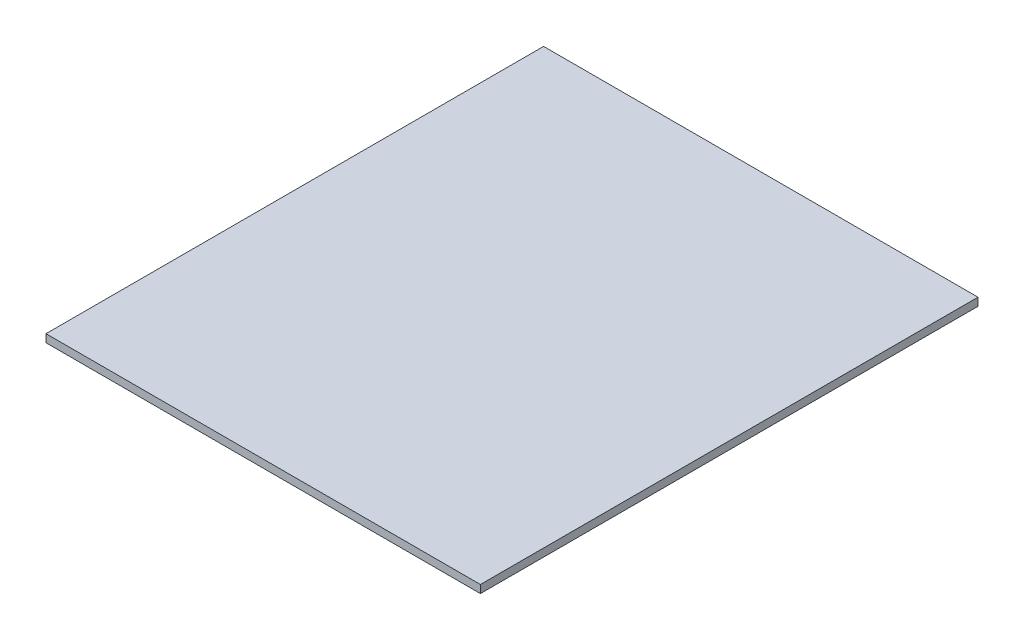
SolidWorks part; units mm, degrees
ref_plane "Front Plane" through (0, 0, 0) normal (0, 0, 1) x (1, 0, 0)
ref_plane "Top Plane" through (0, 0, 0) normal (0, 1, 0) x (1, 0, 0)
ref_plane "Right Plane" through (0, 0, 0) normal (1, 0, 0) x (0, 0, -1)
sketch "Sketch1" plane through (0, 0, 0) normal (0, 1, 0) x (1, 0, 0)
  line L1 (-275, 315) -> (275, 315)
  line L2 (-275, 315) -> (-275, -315)
  line L3 (-275, -315) -> (275, -315)
  line L4 (275, 315) -> (275, -315)
  line L5 (-275, 315) -> (275, -315) construction
  line L6 (-275, -315) -> (275, 315) construction
  point P0 (0, 0)
  dimension "D1" = 630
  dimension "D2" = 550
extrude "Boss-Extrude1" add sketch "Sketch1" along normal blind 10
